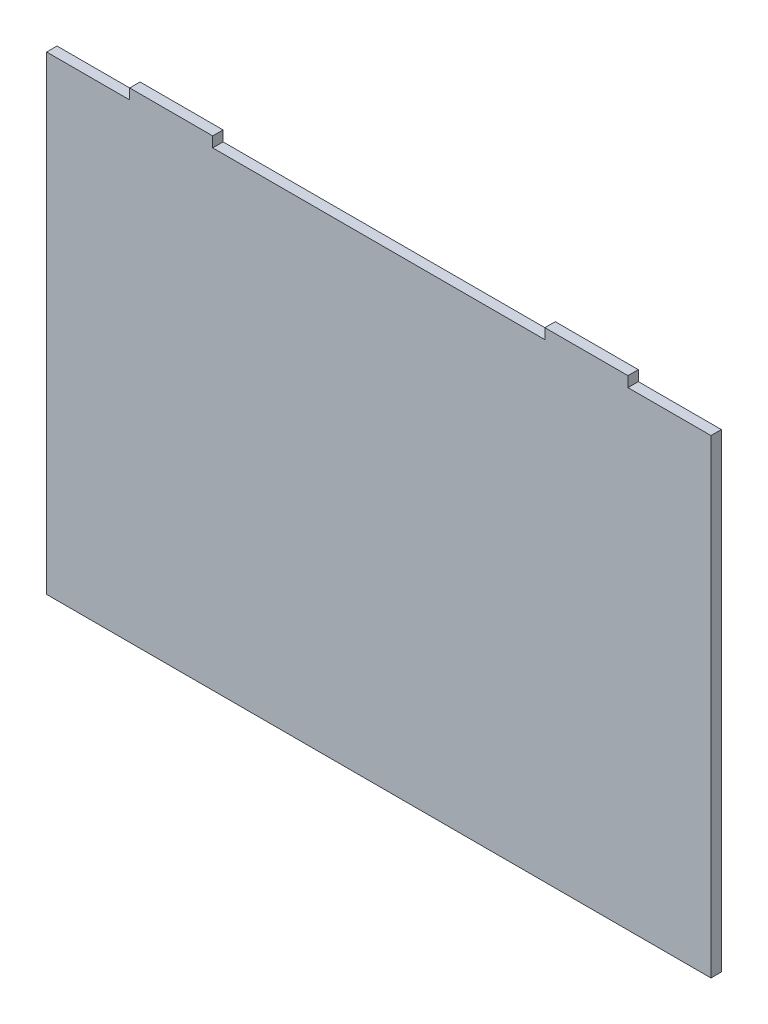
SolidWorks part; units mm, degrees
ref_plane "Front Plane" through (0, 0, 0) normal (0, 0, 1) x (1, 0, 0)
ref_plane "Top Plane" through (0, 0, 0) normal (0, 1, 0) x (1, 0, 0)
ref_plane "Right Plane" through (0, 0, 0) normal (1, 0, 0) x (0, 0, -1)
sketch "Sketch1" plane through (0, 0, 0) normal (0, 0, 1) x (1, 0, 0)
  line L0 (0, 143.6878) -> (25.4, 143.6878)
  line L1 (0, 0) -> (203.2, 0)
  line L2 (0, 0) -> (0, 143.6878)
  line L3 (25.4, 143.6878) -> (25.4, 146.8628)
  line L4 (203.2, 0) -> (203.2, 143.6878)
  line L5 (25.4, 146.8628) -> (50.8, 146.8628)
  line L6 (50.8, 146.8628) -> (50.8, 143.6878)
  line L7 (50.8, 143.6878) -> (152.4, 143.6878)
  line L8 (152.4, 143.6878) -> (152.4, 146.8628)
  line L9 (152.4, 146.8628) -> (177.8, 146.8628)
  line L10 (177.8, 146.8628) -> (177.8, 143.6878)
  line L11 (177.8, 143.6878) -> (203.2, 143.6878)
  dimension "D1" = 203.2
  dimension "D2" = 25.4
  dimension "D3" = 3.175
  dimension "D4" = 143.6878
extrude "Boss-Extrude1" add sketch "Sketch1" along normal blind 3.175
extrude "Boss-Extrude2" add sketch "Sketch1<2>" along normal blind 3.175
sketch "Sketch1<2>" plane through (0, 0, 0) normal (0, 0, 1) x (1, 0, 0) same geometry as "Sketch1"
